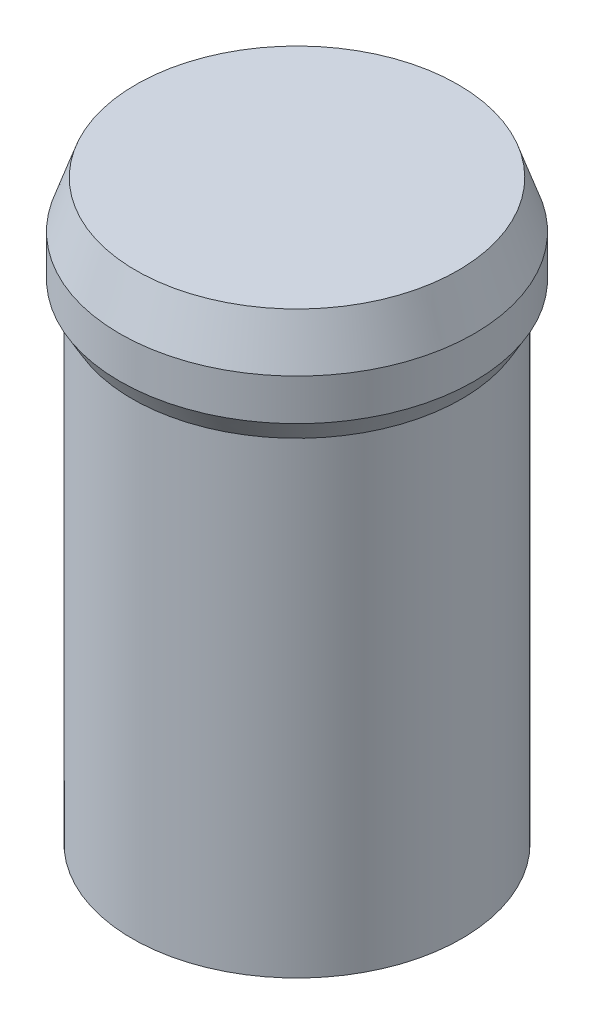
SolidWorks part; units mm, degrees
ref_plane "Front Plane" through (0, 0, 0) normal (0, 0, 1) x (1, 0, 0)
ref_plane "Top Plane" through (0, 0, 0) normal (0, 1, 0) x (1, 0, 0)
ref_plane "Right Plane" through (0, 0, 0) normal (1, 0, 0) x (0, 0, -1)
sketch "Sketch1" plane through (0, 0, 0) normal (0, 0, 1) x (1, 0, 0)
  line L0 (20, 0) -> (20, 56.7271)
  line L1 (20, 56.7271) -> (21.5, 59.3252)
  line L2 (21.5, 59.3252) -> (21.5, 64.3252)
  line L3 (21.5, 64.3252) -> (19.5473, 69.9985)
  line L4 (20, 0) -> (19, 0)
  line L5 (19, 0) -> (19, 1.15)
  line L6 (4.5, 1.15) -> (19, 1.15)
  line L7 (0, 2.4) -> (0, 83.9789) construction
  line L8 (4.5, 2.4) -> (0, 2.4)
  line L9 (4.5, 2.4) -> (4.5, 1.15)
  line L11 (19.5473, 69.9985) -> (0, 69.9985)
  line L12 (0, 69.9985) -> (0, 2.4)
  point P12 (0, 0)
  point P14 (0, 0)
  dimension "D1" = 20
  dimension "D2" = 1
  dimension "D3" = 4.5
  dimension "D4" = 70
  dimension "D5" = 5
  dimension "D6" = 1.5
  dimension "D7" = 3
  dimension "D8" = 6
  dimension "D9" = 1.15
  dimension "D10" = 1.25
revolve "Revolve1" add sketch "Sketch1" angle 360 about L7
fillet "Fillet1" radius 1.5 1 edges at (0, 1.15, -4.5) profile chamfer
